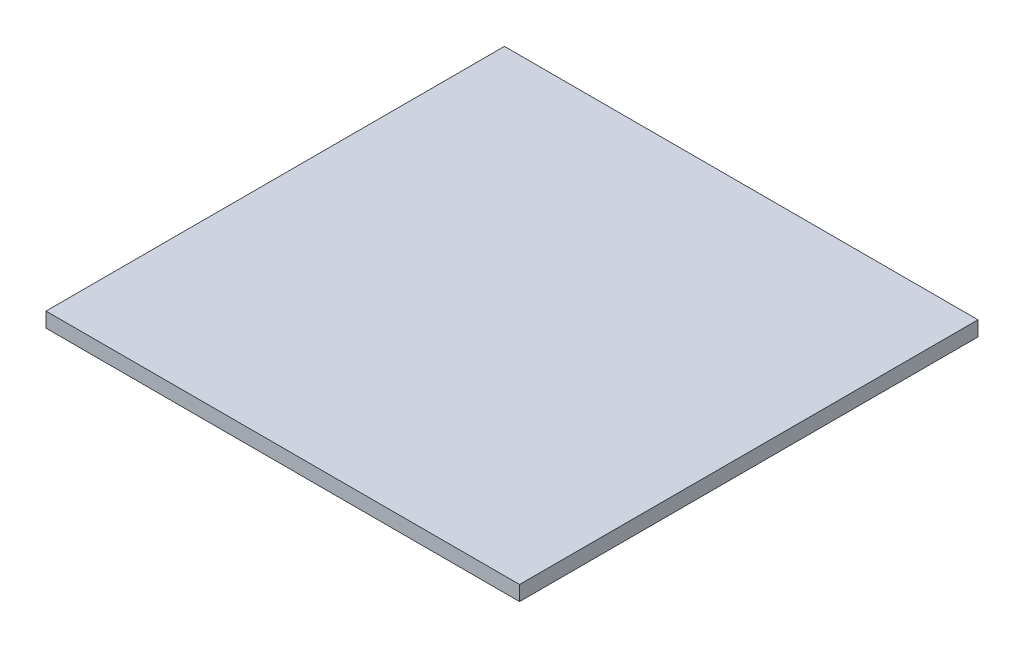
SolidWorks part; units mm, degrees
ref_plane "Front Plane" through (0, 0, 0) normal (0, 0, 1) x (1, 0, 0)
ref_plane "Top Plane" through (0, 0, 0) normal (0, 1, 0) x (1, 0, 0)
ref_plane "Right Plane" through (0, 0, 0) normal (1, 0, 0) x (0, 0, -1)
sketch "Sketch1" plane through (0, 0, 0) normal (0, 1, 0) x (1, 0, 0)
  line L1 (-44.2815, 20.698) -> (57.7785, 20.698)
  line L2 (-44.2815, 20.698) -> (-44.2815, -78.102)
  line L3 (-44.2815, -78.102) -> (57.7785, -78.102)
  line L4 (57.7785, 20.698) -> (57.7785, -78.102)
  dimension "D1" = 102.06
  dimension "D2" = 98.8
extrude "Boss-Extrude1" add sketch "Sketch1" along normal blind 3.2
equation "\"Fit\"= 1"
equation "\"cover width\"= 98.8"
equation "\"bottom 4 length\" = 102.06"
equation "\"thinner acrylic\"= 3.2"
equation "\"D1@Sketch1\"=\"bottom 4 length\""
equation "\"D2@Sketch1\"=\"cover width\""
equation "\"D1@Boss-Extrude1\"=\"thinner acrylic\""
